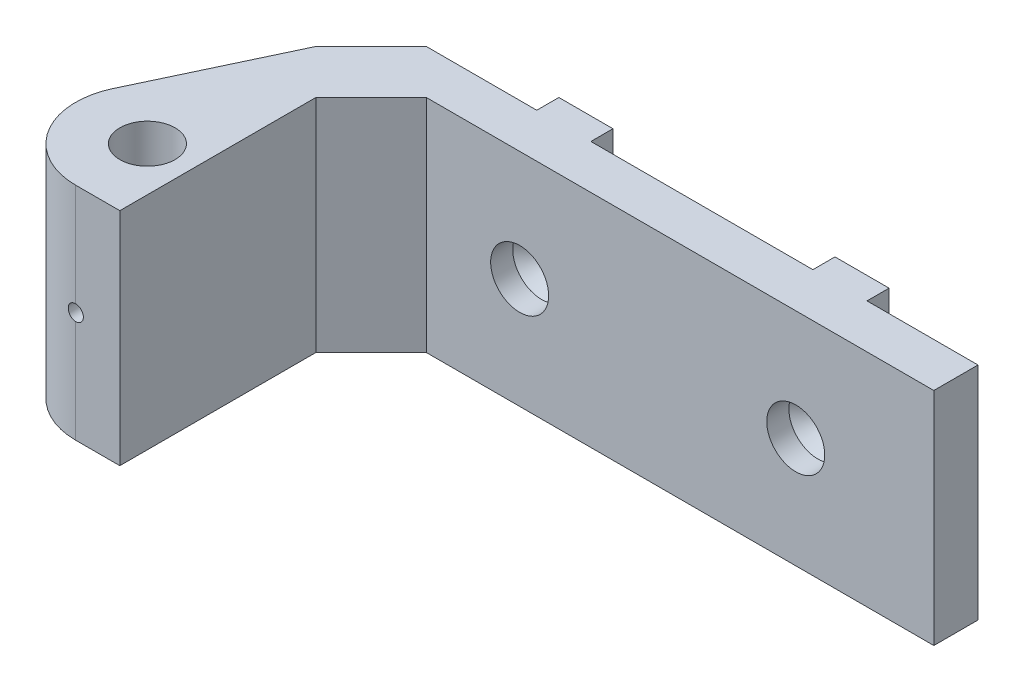
SolidWorks part; units mm, degrees
ref_plane "Top Plane" through (0, 0, 0) normal (0, 0, 1) x (1, 0, 0)
ref_plane "Right Plane" through (0, 0, 0) normal (0, 1, 0) x (1, 0, 0)
ref_plane "Front Plane" through (0, 0, 0) normal (1, 0, 0) x (0, 0, -1)
sketch "Sketch1" plane through (0, 0, 0) normal (0, 0, 1) x (1, 0, 0)
  line L0 (-25, 0) -> (25, 0) construction
  line L2 (-50, -20) -> (50, -20)
  line L3 (-50, -20) -> (-50, 20)
  line L4 (-50, 20) -> (50, 20)
  line L5 (50, -20) -> (50, 20)
  line L6 (-50, -20) -> (50, 20) construction
  line L7 (-50, 20) -> (50, -20) construction
  circle A0 centre (-25, 0) radius 2.75
  circle A1 centre (25, 0) radius 2.75
  point P4 (0, 0)
  point P5 (0, 0)
  dimension "D1" = 5.5
  dimension "D2" = 50
  dimension "D3" = 40
  dimension "D4" = 100
extrude "Boss-Extrude1" add sketch "Sketch1" along normal blind 8
sketch "Sketch2" plane through (0, -20, 0) normal (0, -1, 0) x (1, 0, 0)
  line L0 (-59.9, 27.5) -> (-59.9, 53.5) construction
  line L1 (-50, 0) -> (-59.9, 0)
  line L2 (-50, 0) -> (-50, 8)
  line L3 (-50, 8) -> (-51.9, 8)
  line L6 (-59.9, 0) -> (-59.9, 27.5)
  line L7 (-59.9, 53.5) -> (-51.9, 53.5)
  line L8 (-51.9, 8) -> (-51.9, 53.5)
  line L9 (-50, 0) -> (50, 0) construction
  arc A0 (-59.9, 53.5) -> (-59.9, 27.5) centre (-59.9, 40.5) ccw
  circle A1 centre (-59.9, 40.5) radius 5
  point P13 (0, 0)
  dimension "D2" = 8
  dimension "D4" = 10
  dimension "D1" = 59.9
  dimension "D3" = 40.5
extrude "Boss-Extrude2" add sketch "Sketch2" against normal up to surface (40 mm away) up to face at (0, 20, 4)
chamfer "Chamfer1" distance 10 angle 45 3 edges at (-59.9, 0, 0) (-59.9, 0, 27.5) (-51.9, 0, 8)
sketch "Sketch4" plane through (0, 0, 0) normal (0, 0, -1) x (-1, 0, 0)
  line L0 (49.9, -20) -> (-50, -20) construction
  line L1 (29.9, -20) -> (20.1, -20)
  line L2 (29.9, -20) -> (29.9, 20)
  line L3 (29.9, 20) -> (20.1, 20)
  line L4 (20.1, -20) -> (20.1, 20)
  line L5 (-50, 20) -> (49.9, 20) construction
  line L6 (25, -20) -> (25, 20) construction
  line L7 (0, -20) -> (0, 20) construction
  line L12 (-29.9, 20) -> (-20.1, 20)
  line L13 (-20.1, -20) -> (-20.1, 20)
  line L14 (-29.9, -20) -> (-20.1, -20)
  line L15 (-29.9, -20) -> (-29.9, 20)
  circle A0 centre (-25, 0) radius 2.75
  circle A1 centre (25, 0) radius 2.75 construction
  circle A2 centre (25, 0) radius 2.75
  point P10 (25, 0)
  point P15 (25, 0)
  dimension "D1" = 9.8
extrude "Boss-Extrude3" add sketch "Sketch4" along normal blind 4
sketch "Sketch5" plane through (0, 0, 8) normal (0, 0, 1) x (1, 0, 0)
  circle A0 centre (25, 0) radius 5.25
  circle A1 centre (-25, 0) radius 5.25
  dimension "D1" = 10.5
extrude "Cut-Extrude1" cut sketch "Sketch5" against normal offset from surface (4 mm away) 4 up to face at (39.95, 0, 0)
chamfer "Chamfer2" distance 2.5 angle 45 2 edges at (22.25, 0, 4) (-27.75, 0, 4)
sketch "Sketch6" plane through (0, 0, 53.5) normal (0, 0, 1) x (1, 0, 0)
  line L1 (-59.9, 20) -> (-59.9, -20) construction
  circle A0 centre (-59.9, 0) radius 1.4
  point P2 (-57.2859, -12.2519)
  point P3 (0, 0)
  dimension "D1" = 2.8
extrude "Cut-Extrude2" cut sketch "Sketch6" against normal up to next
sketch "Sketch7" plane through (0, -20, 0) normal (0, -1, 0) x (1, 0, 0)
  line L0 (-59.9, 10) -> (-71.66, 34.959)
  line L1 (-59.9, 10) -> (-59.9, 34.959)
  line L2 (-59.9, 34.959) -> (-71.66, 34.959)
  arc A0 (-59.9, 53.5) -> (-65.5522, 28.793) centre (-59.9, 40.5) ccw construction
extrude "Boss-Extrude4" add sketch "Sketch7" against normal up to surface (40 mm away) up to face at (-19.4833, 20, 10.3241)
